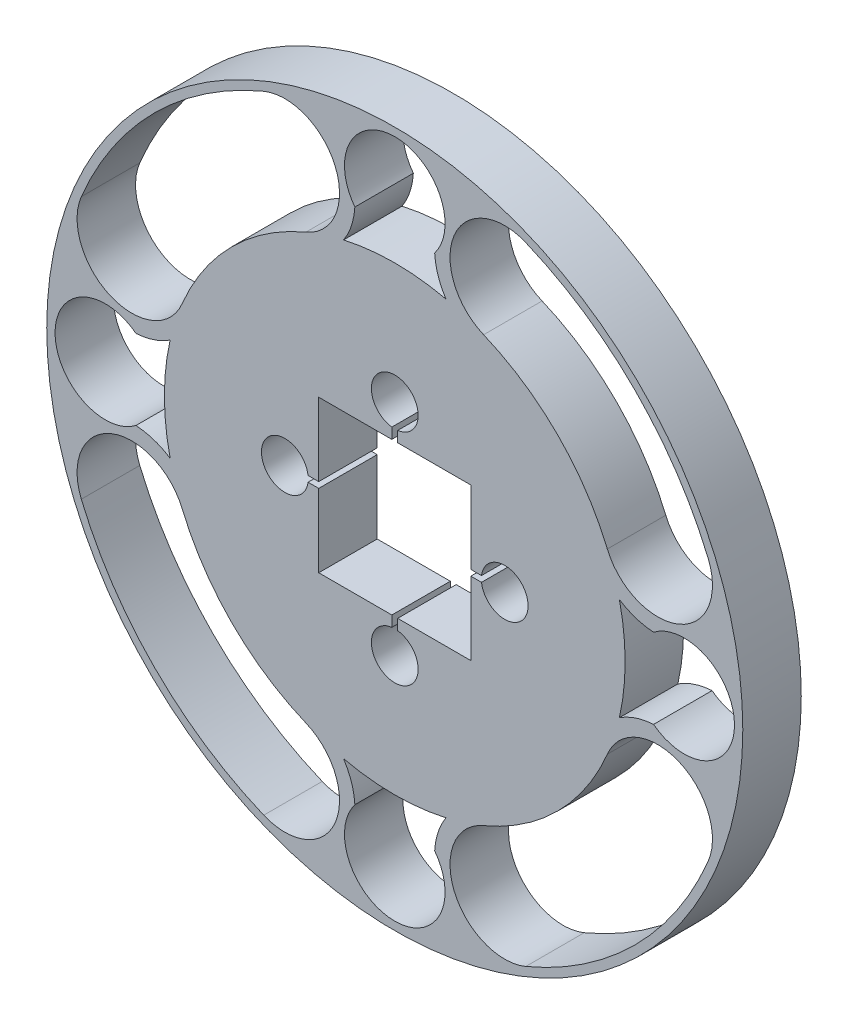
SolidWorks part; units mm, degrees
material "AISI 1020"
ref_plane "Front Plane" through (0, 0, 0) normal (0, 0, 1) x (1, 0, 0)
ref_plane "Top Plane" through (0, 0, 0) normal (0, 1, 0) x (1, 0, 0)
ref_plane "Right Plane" through (0, 0, 0) normal (1, 0, 0) x (0, 0, -1)
other "Center of Mass"
sketch "Sketch1" plane through (0, 0, 0) normal (0, 0, 1) x (1, 0, 0)
  line L0 (-11.938, 0) -> (0, 0) construction
  line L1 (-8.255, 8.255) -> (8.255, 8.255)
  line L2 (-8.255, 8.255) -> (-8.255, -8.255)
  line L3 (-8.255, -8.255) -> (8.255, -8.255)
  line L4 (8.255, 8.255) -> (8.255, -8.255)
  line L5 (0, 0) -> (0, 11.938) construction
  line L6 (11.938, 0) -> (0, 0) construction
  line L7 (0, 0) -> (0, -11.938) construction
  line L9 (-9.4179, 0.3175) -> (9.4179, 0.3175)
  line L10 (-9.4179, 0.3175) -> (-9.4179, -0.3175)
  line L11 (-9.4179, -0.3175) -> (9.4179, -0.3175)
  line L12 (9.4179, 0.3175) -> (9.4179, -0.3175)
  line L13 (-0.3175, 9.4179) -> (0.3175, 9.4179)
  line L14 (-0.3175, 9.4179) -> (-0.3175, -9.4179)
  line L15 (-0.3175, -9.4179) -> (0.3175, -9.4179)
  line L16 (0.3175, 9.4179) -> (0.3175, -9.4179)
  arc A0 (9.6484, -23.0838) -> (23.0838, -9.6484) centre (0, 0) ccw
  circle A1 centre (0, 11.938) radius 2.54
  circle A2 centre (0, -11.938) radius 2.54
  circle A3 centre (11.938, 0) radius 2.54
  circle A4 centre (-11.938, 0) radius 2.54
  arc A5 (14.2276, -34.0397) -> (34.0397, -14.2276) centre (0, 0) ccw
  arc A7 (-34.0397, 14.2276) -> (-23.0838, 9.6484) centre (-28.5618, 11.938) ccw
  arc A8 (-23.0838, -9.6484) -> (-34.0397, -14.2276) centre (-28.5618, -11.938) ccw
  arc A10 (-9.6484, 23.0838) -> (-14.2276, 34.0397) centre (-11.938, 28.5618) ccw
  arc A11 (34.0397, -14.2276) -> (23.0838, -9.6484) centre (28.5618, -11.938) ccw
  arc A13 (-14.2276, -34.0397) -> (-9.6484, -23.0838) centre (-11.938, -28.5618) ccw
  arc A14 (9.6484, -23.0838) -> (14.2276, -34.0397) centre (11.938, -28.5618) ccw
  arc A15 (-23.0838, -9.6484) -> (-9.6484, -23.0838) centre (0, 0) ccw
  arc A16 (-34.0397, -14.2276) -> (-14.2276, -34.0397) centre (0, 0) ccw
  arc A19 (-9.6484, 23.0838) -> (-23.0838, 9.6484) centre (0, 0) ccw
  arc A20 (-14.2276, 34.0397) -> (-34.0397, 14.2276) centre (0, 0) ccw
  arc A23 (23.0838, 9.6484) -> (34.0397, 14.2276) centre (28.5618, 11.938) ccw [skipped]
  arc A24 (14.2276, 34.0397) -> (9.6484, 23.0838) centre (11.938, 28.5618) ccw [skipped]
  arc A25 (-9.6484, 23.0838) -> (-14.2276, 34.0397) centre (-11.938, 28.5618) ccw
  arc A26 (-34.0397, 14.2276) -> (-23.0838, 9.6484) centre (-28.5618, 11.938) ccw
  arc A27 (-14.2276, 34.0397) -> (-34.0397, 14.2276) centre (0, 0) ccw
  arc A28 (23.0838, 9.6484) -> (34.0397, 14.2276) centre (28.5618, 11.938) ccw
  arc A29 (14.2276, 34.0397) -> (9.6484, 23.0838) centre (11.938, 28.5618) ccw
  arc A30 (34.0397, 14.2276) -> (14.2276, 34.0397) centre (0, 0) ccw
  arc A31 (9.6484, -23.0838) -> (14.2276, -34.0397) centre (11.938, -28.5618) ccw
  arc A32 (34.0397, -14.2276) -> (23.0838, -9.6484) centre (28.5618, -11.938) ccw
  arc A33 (14.2276, -34.0397) -> (34.0397, -14.2276) centre (0, 0) ccw
  arc A34 (-9.6484, 23.0838) -> (-23.0838, 9.6484) centre (0, 0) ccw
  arc A35 (23.0838, 9.6484) -> (9.6484, 23.0838) centre (0, 0) ccw
  arc A36 (9.6484, -23.0838) -> (23.0838, -9.6484) centre (0, 0) ccw
  circle A43 centre (0, 0) radius 37.7952
  arc A44 (4.3316, 28.1069) -> (-4.3316, 28.1069) centre (0, 31.4325) ccw
  arc A45 (28.1069, -4.3316) -> (28.1069, 4.3316) centre (31.4325, 0) ccw
  circle A46 centre (0, -31.4325) radius 5.461
  arc A47 (-28.1069, 4.3316) -> (-28.1069, -4.3316) centre (-31.4325, 0) ccw
  arc A48 (-9.6484, 23.0838) -> (-23.0838, 9.6484) centre (0, 0) ccw
  arc A49 (-23.0838, -9.6484) -> (-9.6484, -23.0838) centre (0, 0) ccw
  arc A50 (9.6484, -23.0838) -> (23.0838, -9.6484) centre (0, 0) ccw
  arc A51 (28.1069, -4.3316) -> (24.3936, -5.5591) centre (28.5618, -11.938) ccw
  arc A53 (24.3936, 5.5591) -> (28.1069, 4.3316) centre (28.5618, 11.938) ccw
  arc A54 (23.0838, 9.6484) -> (9.6484, 23.0838) centre (0, 0) ccw
  arc A55 (24.3936, -5.5591) -> (24.3936, 5.5591) centre (0, 0) ccw
  arc A56 (5.5591, -24.3936) -> (4.3316, -28.1069) centre (11.938, -28.5618) ccw
  arc A57 (-5.5591, -24.3936) -> (5.5591, -24.3936) centre (0, 0) ccw
  arc A58 (-4.3316, -28.1069) -> (-5.5591, -24.3936) centre (-11.938, -28.5618) ccw
  arc A59 (-4.3316, -28.1069) -> (4.3316, -28.1069) centre (0, -31.4325) ccw
  arc A60 (-24.3936, -5.5591) -> (-28.1069, -4.3316) centre (-28.5618, -11.938) ccw
  arc A61 (-24.3936, 5.5591) -> (-24.3936, -5.5591) centre (0, 0) ccw
  arc A62 (-28.1069, 4.3316) -> (-24.3936, 5.5591) centre (-28.5618, 11.938) ccw
  arc A63 (-28.1069, 4.3316) -> (-28.1069, -4.3316) centre (-31.4325, 0) ccw
  arc A64 (-5.5591, 24.3936) -> (-4.3316, 28.1069) centre (-11.938, 28.5618) ccw
  arc A65 (5.5591, 24.3936) -> (-5.5591, 24.3936) centre (0, 0) ccw
  arc A66 (4.3316, 28.1069) -> (5.5591, 24.3936) centre (11.938, 28.5618) ccw
  arc A67 (4.3316, 28.1069) -> (-4.3316, 28.1069) centre (0, 31.4325) ccw
  point P7 (8.255, 0)
  point P8 (0, 8.255)
  point P54 (0, 0)
  point P70 (0, 0)
  point P77 (0, 0)
  point P104 (0, 0)
  dimension "D2" = 50.038
  dimension "D4" = 5.08
  dimension "D6" = 73.787
  dimension "D7" = 4
  dimension "D10" = 75.5904
  dimension "D11" = 10.922
  dimension "D12" = 7.62
  dimension "D13" = 4
  dimension "D1" = 16.51
  dimension "D3" = 11.938
  dimension "D5" = 0.635
  dimension "D9" = 4
  dimension "D8" = 4
extrude "Boss-Extrude1" add sketch "Sketch1" along normal blind 6.35 contours A0 A4 L9 L2 L1 L14 A1 L16 L4 A3 L11 L3 A2 region at (-37.6883, 0, 0)
